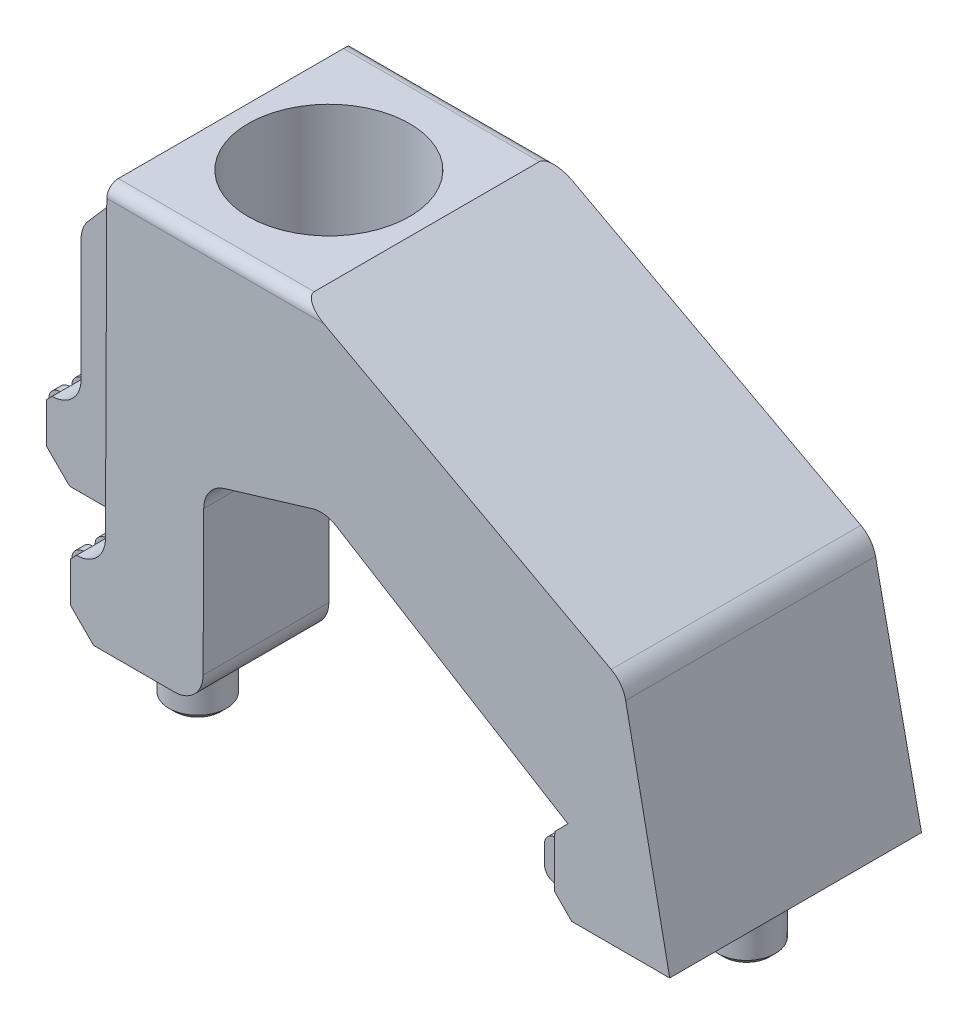
SolidWorks part; units mm, degrees
material "PLA"
ref_plane "Front Plane" through (0, 0, 0) normal (0, 0, 1) x (1, 0, 0)
ref_plane "Top Plane" through (0, 0, 0) normal (0, 1, 0) x (1, 0, 0)
ref_plane "Right Plane" through (0, 0, 0) normal (1, 0, 0) x (0, 0, -1)
sketch "Sketch1" plane through (0, 0, 0) normal (0, 0, 1) x (1, 0, 0)
  line L1 (14.2587, 0) -> (-14.2587, 0) construction
  line L3 (0, 0) -> (0, 20)
  line L4 (0, 20) -> (13, 35)
  line L5 (13, 35) -> (30, 35)
  line L6 (30, 35) -> (57.8582, 20)
  line L7 (57.8582, 20) -> (62, 0)
  line L8 (62, 0) -> (55, 0)
  line L9 (55, 0) -> (55, 6)
  line L12 (32, 20) -> (7, 12.5)
  line L13 (7, 12.5) -> (7, 0)
  line L14 (7, 0) -> (0, 0)
  line L16 (55, 6) -> (32, 20)
  dimension "D1" = 48
  dimension "D2" = 7
  dimension "D3" = 17
  dimension "D4" = 7
  dimension "D5" = 6
  dimension "D6" = 35
  dimension "D7" = 15
  dimension "D8" = 12.5
  dimension "D9" = 25
  dimension "D10" = 14
  dimension "D11" = 15
  dimension "D12" = 130
  dimension "D13" = 30
extrude "Boss-Extrude2" add sketch "Sketch1" along normal blind 30 contours L16 L12 L13 L14 L3 L4 L5 L6 L7 L8 L9
sketch "Sketch2" plane through (0, 0, 30) normal (0, 0, 1) x (1, 0, 0)
  line L0 (21.5, 35) -> (21.5, 16.85)
  line L1 (13, 35) -> (30, 35) construction
  line L2 (32, 20) -> (7, 12.5) construction
  line L3 (21.5, 16.85) -> (7, 12.5)
  line L4 (7, 12.5) -> (7, 0)
  line L5 (7, 0) -> (0, 0)
  line L6 (0, 0) -> (0, 20)
  line L7 (0, 20) -> (13, 35)
  line L8 (13, 35) -> (21.5, 35)
extrude "Cut-Extrude1" cut sketch "Sketch2" against normal blind 15
sketch "Sketch3" plane through (0, 0, 15) normal (0, 0, 1) x (1, 0, 0)
  line L0 (21.5, 35) -> (13, 35)
  line L1 (13, 35) -> (13, 16.85)
  line L2 (13, 16.85) -> (21.5, 16.85)
  line L3 (21.5, 35) -> (21.5, 16.85)
extrude "Boss-Extrude3" add sketch "Sketch3" along direction (0, 0, 1) on the side of the normal up to vertex (15 mm away) contours L2 L3 L0 L1 up to point (21.5, 16.85, 30)
sketch "Sketch5" plane through (0, 16.85, 0) normal (0, -1, 0) x (1, 0, 0)
  line L0 (13, 15) -> (13, 30)
  line L1 (13, 30) -> (21.5, 30) construction
  line L2 (13, 30) -> (13, 15) construction
  line L3 (13, 30) -> (21.5, 30)
  line L4 (21.5, 30) -> (21.5, 15)
  line L5 (21.5, 15) -> (13, 15)
extrude "Boss-Extrude4" add sketch "Sketch5" along normal up to vertex (16.85 mm away) contours L3 L4 L5 L0 up to point (7, 0, 15)
sketch "Sketch6" plane through (13, 0, 0) normal (-1, 0, 0) x (0, 0, 1)
  line L0 (15, 0) -> (15, 6)
  line L1 (15, 0) -> (15, 14.3) construction
  line L2 (15, 6) -> (30, 6)
  line L3 (30, 35) -> (30, 0) construction
  line L4 (30, 6) -> (30, 0)
  line L5 (30, 0) -> (15, 0)
  dimension "D1" = 6
extrude "Boss-Extrude5" add sketch "Sketch6" along normal blind 3 contours L2 L4 L5 L0
sketch "Sketch7" plane through (0, 0, 0) normal (-1, 0, 0) x (0, 0, 1)
  line L0 (0, 0) -> (0, 6)
  line L1 (0, 0) -> (0, 20) construction
  line L2 (0, 6) -> (15, 6)
  line L3 (15, 20) -> (15, 0) construction
  line L4 (15, 6) -> (15, 0)
  line L5 (15, 0) -> (0, 0)
  dimension "D1" = 6
extrude "Boss-Extrude6" add sketch "Sketch7" along normal blind 3 contours L2 L4 L5 L0
sketch "Sketch8" plane through (55, 0, 0) normal (-1, 0, 0) x (0, 0, 1)
  line L0 (0, 0) -> (0, 6)
  line L1 (0, 6) -> (30, 6)
  line L2 (30, 6) -> (30, 0)
  line L3 (30, 0) -> (0, 0)
extrude "Boss-Extrude7" add sketch "Sketch8" along normal blind 3 contours L3 L0 L1 L2
chamfer "Chamfer1" distance 2 angle 45 2 edges at (-3, 0, 7.5) (10, 0, 22.5)
chamfer "Chamfer2" distance 1.5 angle 45 1 edges at (52, 0, 15)
chamfer "Chamfer3" distance 3 angle 45 1 edges at (55, 6, 15) first distance on face at (53.5, 6, 15)
chamfer "Chamfer4" distance 0.5 angle 45 2 edges at (10, 6, 22.5) (-3, 6, 7.5)
sketch "Sketch9" plane through (-3, 0, 0) normal (-1, 0, 0) x (0, 0, 1)
  line L0 (1, 2) -> (1, 5.5)
  line L3 (1, 5.5) -> (1.7973, 5.5)
  line L4 (15, 5.5) -> (0, 5.5) construction
  line L5 (1.7973, 5.5) -> (1.7973, 2)
  line L6 (0, 2) -> (15, 2) construction
  line L7 (1.7973, 2) -> (1, 2)
  dimension "D1" = 0.7973
  dimension "D2" = 1
  dimension "D3" = 0.7973
extrude "Boss-Extrude8" add sketch "Sketch9" along normal blind 1 contours L5 L7 L0 L3
fillet "Fillet1" radius 1 2 edges at (-4, 5.5, 1.3987) (-4, 2, 1.3987)
pattern_linear "LPattern2" count 7 spacing 2 along (0, 0, 1) of "Boss-Extrude8", "Fillet1"
sketch "Sketch11" plane through (10, 0, 0) normal (-1, 0, 0) x (0, 0, 1)
  line L0 (16, 2) -> (16, 5.5)
  line L1 (15, 2) -> (30, 2) construction
  line L3 (16, 5.5) -> (16.7973, 5.5)
  line L4 (30, 5.5) -> (15, 5.5) construction
  line L5 (16.7973, 5.5) -> (16.7973, 2)
  line L7 (16.7973, 2) -> (16, 2)
  dimension "D1" = 0.7973
  dimension "D2" = 1
  dimension "D3" = 0.7973
extrude "Boss-Extrude9" add sketch "Sketch11" along normal blind 1 contours L5 L7 L0 L3
fillet "Fillet2" radius 1 2 edges at (9, 2, 16.3987) (9, 5.5, 16.3987)
pattern_linear "LPattern3" count 7 spacing 2 along (0, 0, 1) of "Fillet2", "Boss-Extrude9"
sketch "Sketch12" plane through (52, 0, 0) normal (-1, 0, 0) x (0, 0, 1)
  line L0 (1, 2) -> (1, 5.5)
  line L3 (1, 5.5) -> (1.7973, 5.5)
  line L4 (16.7973, 2) -> (18, 2) construction
  line L5 (1.7973, 5.5) -> (1.7973, 2)
  line L6 (18, 5.5) -> (16.7973, 5.5) construction
  line L7 (1.7973, 2) -> (1, 2)
  dimension "D1" = 0.7973
  dimension "D2" = 1
  dimension "D3" = 0.7973
extrude "Boss-Extrude10" add sketch "Sketch12" along normal blind 1 contours L5 L7 L0 L3
fillet "Fillet3" radius 1 2 edges at (51, 2, 1.3987) (51, 5.5, 1.3987)
pattern_linear "LPattern4" count 14 spacing 2 along (0, 0, 1) skipping (6, 0), (7, 0) of "Fillet3", "Boss-Extrude10"
fillet "Fillet4" radius 2.5 9 edges at (7, 0, 7.5) (21.5, 0, 22.5) (7, 12.5, 7.5) (21.5, 16.85, 22.5) (32, 20, 15) (57.8582, 20, 15) (13, 6, 22.5) (0, 6, 7.5) (0, 20, 7.5)
sketch "Sketch13" plane through (0, 35, 0) normal (0, 1, 0) x (1, 0, 0)
  line L0 (30, -30) -> (30, 0) construction
  circle A0 centre (21.5, -15) radius 7
  point P5 (30, -15)
  dimension "D1" = 14
  dimension "D2" = 21.5
extrude "Cut-Extrude4" cut sketch "Sketch13" against normal blind 15 contours A0
sketch "Sketch14" plane through (0, 0, 0) normal (0, -1, 0) x (1, 0, 0)
  line L2 (13, 15) -> (23.2816, 15) construction
  line L3 (19, 15) -> (19, 30) construction
  circle A0 centre (15.5126, 20.39) radius 2.5
  dimension "D1" = 5
  dimension "D2" = 5.39
  dimension "D3" = 3.4874
extrude "Boss-Extrude11" add sketch "Sketch14" along normal blind 5 contours A0
fillet "Fillet5" radius 0.5 1 edges at (15.5126, 0, 22.89)
chamfer "Chamfer5" distance 0.5 angle 45 1 edges at (15.5126, -5, 17.89)
sketch "Sketch15" plane through (0, 0, 0) normal (0, -1, 0) x (1, 0, 0)
  line L0 (62, 0) -> (53.5, 0) construction
  line L1 (62, 0) -> (53.5, 0) construction
  circle A0 centre (57.75, 15) radius 2.5
  point P8 (57.75, 0)
  dimension "D1" = 5
  dimension "D3" = 15
extrude "Boss-Extrude12" add sketch "Sketch15" along normal blind 5 contours A0
fillet "Fillet6" radius 0.5 1 edges at (57.75, 0, 12.5)
chamfer "Chamfer6" distance 0.5 angle 45 1 edges at (57.75, -5, 12.5)
sketch "Sketch16" plane through (0, 0, 0) normal (0, -1, 0) x (-1, 0, 0)
  line L0 (-4.5, 0) -> (1, 0) construction
  line L1 (1, 0) -> (-1.75, 0)
  line L2 (1, -15) -> (-4.5, -15) construction
  circle A0 centre (-1.75, -9.61) radius 2.5
  dimension "D1" = 5
  dimension "D2" = 5.39
extrude "Boss-Extrude13" add sketch "Sketch16" along normal blind 5 contours A0
fillet "Fillet7" radius 0.5 1 edges at (1.75, 0, 7.11)
chamfer "Chamfer7" distance 0.5 angle 45 1 edges at (1.75, -5, 7.11)
chamfer "Chamfer8" distance 4 angle 45 2 edges at (21.5, 35, 30) (21.5, 35, 0)
fillet "Fillet8" radius 2 2 edges at (25.2144, 31, 30) (23.4811, 31, 0)
sketch "Sketch17" plane through (0, 0, 0) normal (1, 0, 0) x (0, 0, -1)
  line L0 (-25.9248, 0) -> (-25.7654, 35)
  line L1 (-26, 35) -> (-15, 35) construction
  line L2 (-25.7654, 35) -> (-30.1827, 35)
  line L3 (-30.1827, 35) -> (-30.3421, 0)
  line L4 (16.5, 0) -> (-16.5, 0) construction
  line L5 (-30.3421, 0) -> (-25.9248, 0)
  dimension "D1" = 4.4173
  dimension "D2" = 25.9248
  dimension "D3" = 25.7654
extrude "Cut-Extrude5" cut sketch "Sketch17" along normal through all both and the other way through all contours L3 L5 L0 L2
ref_plane "Plane1" through (0, 0, 15) normal (0, 0, 1) x (1, 0, 0)
mirror "Mirror2" about plane through (0, 0, 15) normal (0, 0, 1) of "Cut-Extrude5"
fillet "Fillet9" radius 1 2 edges at (21.5, 35, 4.2346) (21.5, 35, 25.7654)
sketch "Sketch18" plane through (0, -0.0186, 4.0751) normal (0, 0.0046, -1) x (-1, 0, 0)
  text T0 "ME 1670" font "ROG Fonts" height 1.5
  dimension "D1" = 31.25
  dimension "D2" = 15
extrude "Boss-Extrude15" add sketch "Sketch18" along normal blind 0.5
